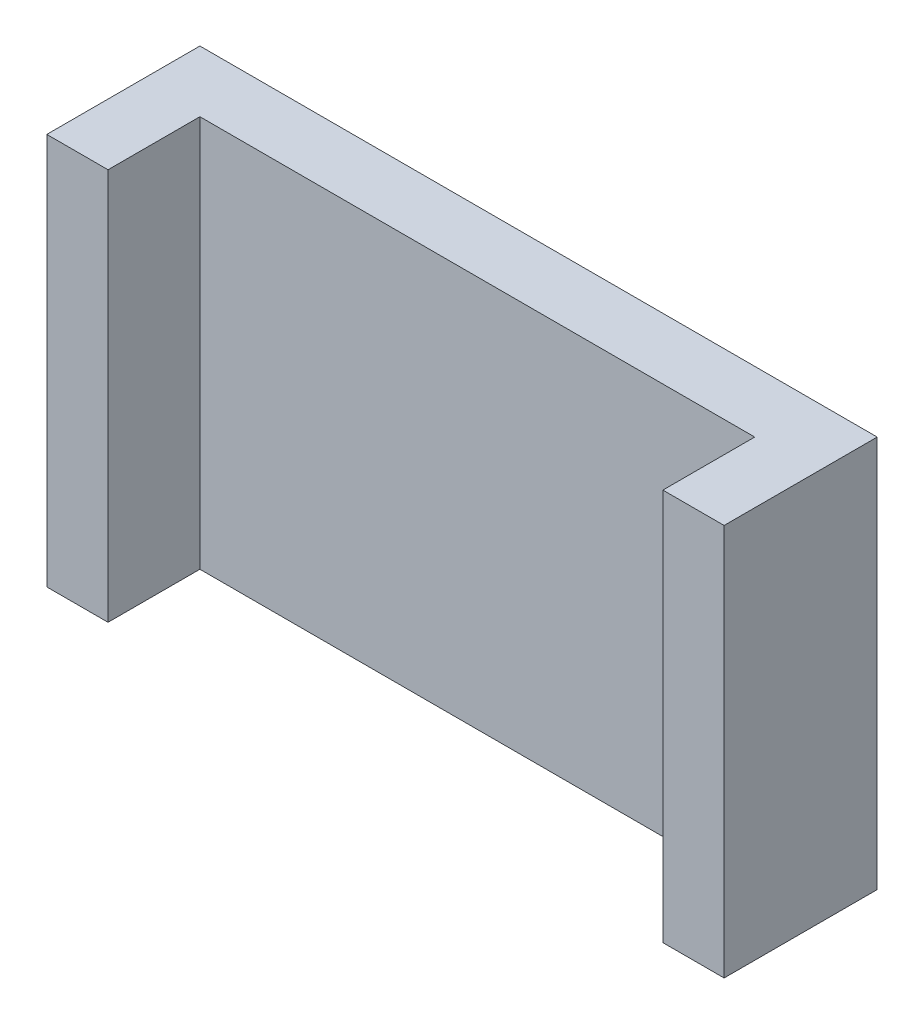
SolidWorks part; units mm, degrees
ref_plane "Front Plane" through (0, 0, 0) normal (0, 0, 1) x (1, 0, 0)
ref_plane "Top Plane" through (0, 0, 0) normal (0, 1, 0) x (1, 0, 0)
ref_plane "Right Plane" through (0, 0, 0) normal (1, 0, 0) x (0, 0, -1)
sketch "Sketch1" plane through (0, 0, 0) normal (0, 0, 1) x (1, 0, 0)
  line L1 (0, 0) -> (55.3, 0)
  line L2 (0, 0) -> (0, 32)
  line L3 (0, 32) -> (55.3, 32)
  line L4 (55.3, 0) -> (55.3, 32)
extrude "Boss-Extrude1" add sketch "Sketch1" along normal blind 5 contours L3 L4 L1 L2
sketch "Sketch2" plane through (0, 0, 5) normal (0, 0, 1) x (1, 0, 0)
  line L0 (0, 0) -> (55.3, 0) construction
  line L1 (0, 32) -> (5, 32)
  line L2 (0, 32) -> (0, 0)
  line L3 (0, 0) -> (5, 0)
  line L4 (5, 32) -> (5, 0)
  line L10 (55.3, 32) -> (50.3, 32)
  line L11 (55.3, 32) -> (55.3, 0)
  line L12 (55.3, 0) -> (50.3, 0)
  line L13 (50.3, 32) -> (50.3, 0)
  line M9 (0, 32) -> (0, 0)
  line M10 (0, 0) -> (55.3, 0)
  line M12 (55.3, 32) -> (0, 32)
extrude "Boss-Extrude2" add sketch "Sketch2" along normal blind 7.5 contours L4 M12 M9 M10 | L10 L13 L12 L11 region at (2.5, 16, 5)
